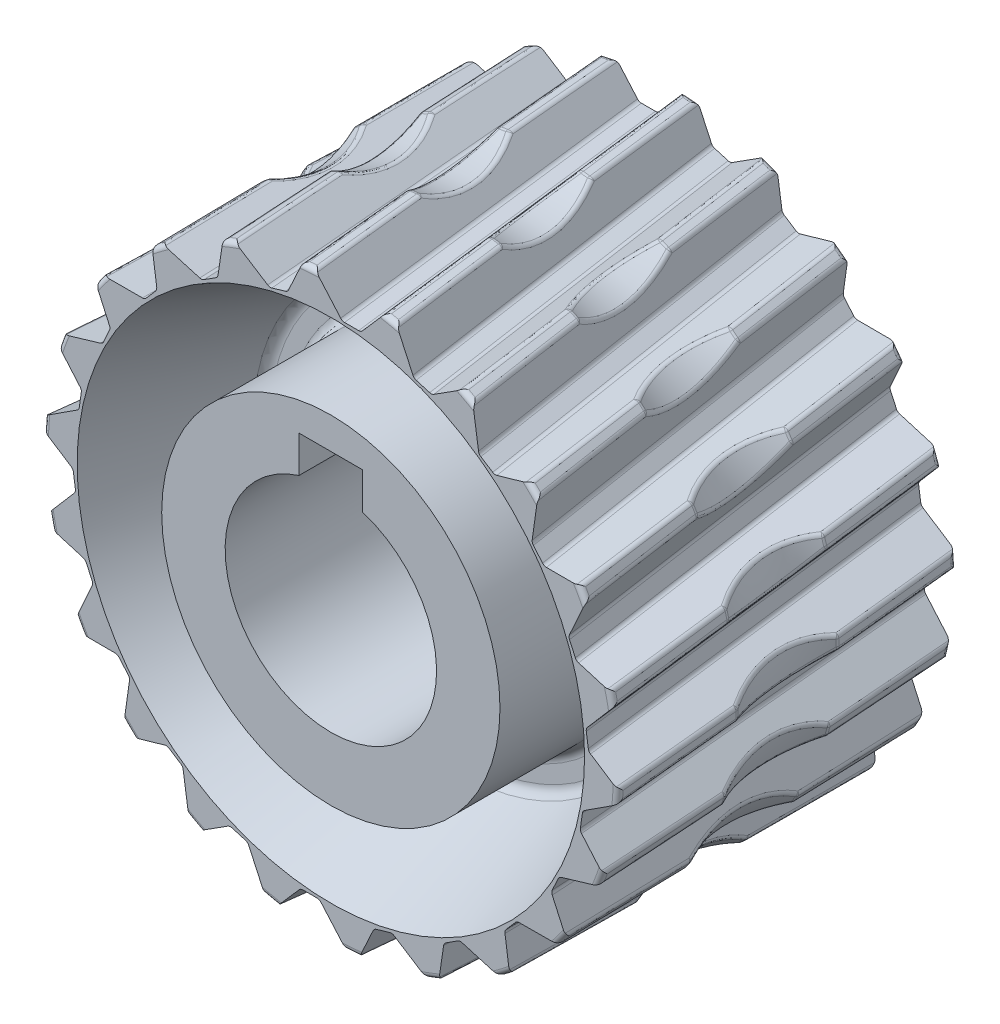
SolidWorks part; units mm, degrees
material "AISI 1020"
ref_plane "Front Plane" through (0, 0, 0) normal (0, 0, 1) x (1, 0, 0)
ref_plane "Top Plane" through (0, 0, 0) normal (0, 1, 0) x (1, 0, 0)
ref_plane "Right Plane" through (0, 0, 0) normal (1, 0, 0) x (0, 0, -1)
sketch "Base Sketch" plane through (0, 0, 0) normal (0, 0, 1) x (1, 0, 0)
  circle A0 centre (0, 0) radius 28.575
  circle A1 centre (0, 0) radius 7.9375
  dimension "D1" = 57.15
  dimension "D2" = 15.875
extrude "Base" add sketch "Base Sketch" along normal mid plane 25.4
sketch "Groove Sketch" plane through (0, 0, 0) normal (1, 0, 0) x (0, 0, -1)
  line L0 (12.7, 28.575) -> (-12.7, 28.575) construction
  line L1 (0, 0) -> (25.0554, 0) construction
  circle A0 centre (0, 28.575) radius 7.9375
  dimension "D1" = 15.875
revolve "Groove" cut sketch "Groove Sketch" angle 360 about L1
sketch "Revolved Sketch" plane through (0, 0, 0) normal (1, 0, 0) x (0, 0, -1)
  line L0 (12.7, 12.7) -> (2.54, 12.7)
  line L1 (12.7, -28.575) -> (12.7, 28.575) construction
  line L2 (2.54, 12.7) -> (2.54, 15.24)
  line L3 (2.54, 15.24) -> (12.7, 19.05)
  line L4 (12.7, 19.05) -> (12.7, 12.7)
  line L5 (0, 0) -> (27.599, 0) construction
  line L6 (0, 0) -> (0, 38.1046) construction
  line L7 (-12.7, 19.05) -> (-12.7, 12.7)
  line L8 (-12.7, 12.7) -> (-2.54, 12.7)
  line L9 (-2.54, 12.7) -> (-2.54, 15.24)
  line L10 (-2.54, 15.24) -> (-12.7, 19.05)
  dimension "D1" = 2.54
  dimension "D2" = 10.16
  dimension "D3" = 38.1
  dimension "D4" = 25.4
revolve "Inner Revolved Cut" cut sketch "Revolved Sketch" angle 360 about L5
chamfer "Outer Chamfer" distance 2.54 angle 45 2 edges at (28.575, 0, -12.7) (28.575, 0, 12.7)
fillet "Inner Fillet" radius 0.7874 4 edges at (15.24, 0, -2.54) (12.7, 0, -2.54) (12.7, 0, 2.54) (15.24, 0, 2.54)
sketch "Keyway Sketch" plane through (0, 0, 0) normal (0, 0, 1) x (1, 0, 0)
  line L1 (2.3876, 0) -> (-2.3876, 0)
  line L2 (2.3876, 0) -> (2.3876, 10.3251)
  line L3 (2.3876, 10.3251) -> (-2.3876, 10.3251)
  line L4 (-2.3876, 0) -> (-2.3876, 10.3251)
  line L5 (2.3876, 0) -> (-2.3876, 10.3251) construction
  line L6 (2.3876, 10.3251) -> (-2.3876, 0) construction
  circle A1 centre (0, 0) radius 7.9375 construction
  point P0 (0, 5.1626)
  dimension "D1" = 4.7752
  dimension "D2" = 2.3876
extrude "Keyway" cut sketch "Keyway Sketch" against normal through all and the other way through all
ref_plane "Hovering Plane" through (0, 24.13, 0) normal (0, 1, 0) x (1, 0, 0)
sketch "Path" plane through (0, 24.13, 0) normal (0, 1, 0) x (1, 0, 0)
  line L0 (0, 12.7) -> (0, -12.7) construction
  line L1 (26.035, 12.7) -> (-26.035, 12.7) construction
  line L2 (-26.035, -12.7) -> (26.035, -12.7) construction
  line L3 (1.9492, -15.875) -> (-1.9492, 15.875)
  point P10 (0, 0)
  dimension "D1" = 7
  dimension "D2" = 3.175
ref_plane "Profile Plane" through (1.9492, 24.13, 15.875) normal (-0.1219, 0, -0.9925) x (-0.9925, 0, 0.1219)
sketch "Revolve Sketch" plane through (0, 0, 0) normal (1, 0, 0) x (0, 0, -1)
  line L0 (0, 0) -> (-12.7, 0) construction
  line L1 (7.9375, 28.575) -> (12.7, 28.575)
  line L2 (12.7, 28.575) -> (12.7, 21.59)
  line L3 (12.7, -26.035) -> (12.7, 26.035) construction
  line L4 (12.7, 21.59) -> (-12.7, 21.59)
  line L5 (-12.7, 26.035) -> (-12.7, -26.035) construction
  line L6 (-12.7, 21.59) -> (-12.7, 28.575)
  line L7 (-12.7, 28.575) -> (7.9375, 28.575)
  line L8 (-12.7, 0) -> (12.7, 0) construction
  dimension "D1" = 43.18
  dimension "D2" = 6.985
  dimension "D3" = 6.985
sketch "Sketch3" plane through (1.9492, 24.13, 15.875) normal (-0.1219, 0, -0.9925) x (-0.9925, 0, 0.1219)
  line L0 (0.6985, -4.9022) -> (-0.6985, -4.9022)
  line L1 (-0.6985, -4.9022) -> (-4.9471, 0)
  line L2 (-4.9471, 0) -> (4.9471, 0)
  line L3 (4.9471, 0) -> (0.6985, -4.9022)
  point P2 (-2.3495, -2.9972)
  point P5 (2.3495, -2.9972)
  point P6 (0, 0)
  point P7 (0, 0)
  dimension "D1" = 2.9972
  dimension "D2" = 1.397
  dimension "D3" = 1.905
  dimension "D4" = 4.699
sweep "Triangle Cut" cut profiles "Sketch3" path "Path"
revolve "Revolve Cut" cut sketch "Revolve Sketch" angle 360 about L0
fillet "Revolved Fillet" radius 0.381 2 edges at (-0.7037, 19.2278, 0) (0.7037, 19.2278, 0)
pattern_circular "Gears" count 22 over 360 about axis through (0, 0, -12.7) along (0, 0, 1) of "Triangle Cut", "Revolved Fillet"
fillet "Groove Fillet" radius 0.381 220 edges at (3.5213, 21.3009, 8.204) (2.6225, 21.4301, -8.204) (4.4401, 21.1285, 8.2746) (4.472, 21.1218, 12.7) (1.6924, 21.5236, -8.2746) (1.6598, 21.5261, -12.7) (-3.5213, 21.3009, -8.204) (-2.6225, 21.4301, 8.204) (-4.4401, 21.1285, -8.2746) (-4.472, 21.1218, -12.7) (-1.6924, 21.5236, 8.2746) (-1.6598, 21.5261, 12.7) (-9.3798, 19.446, -8.204) (-7.6877, 20.1749, 8.2746) (-8.5539, 19.8232, 8.204) (-10.2128, 19.0217, -8.2746) (-10.2416, 19.0063, -12.7) (-7.6572, 20.1865, 12.7) (-14.4784, 16.0157, -8.204) (-13.0602, 17.1918, 8.2746) (-13.7922, 16.6103, 8.204) (-15.1582, 15.3739, -8.2746) (-15.1814, 15.351, -12.7) (-13.0342, 17.2116, 12.7) (-18.4041, 11.2879, -8.204) (-17.3747, 12.8159, 8.2746) (-17.9132, 12.0518, 8.204) (-18.8755, 10.4806, -8.2746) (-18.8913, 10.4521, -12.7) (-17.3553, 12.8422, 12.7) (-20.8388, 5.6457, -8.204) (-20.2816, 7.4018, 8.2746) (-20.583, 6.5169, 8.204) (-21.0636, 4.7383, -8.2746) (-21.0708, 4.7064, -12.7) (-20.2703, 7.4325, 12.7) (-21.5852, -0.454, -8.204) (-21.5453, 1.388, 8.2746) (-21.5852, 0.454, 8.204) (-21.5453, -1.388, -8.2746) (-21.5432, -1.4206, -12.7) (-21.5432, 1.4206, 12.7) (-20.583, -6.5169, -8.204) (-21.0636, -4.7383, 8.2746) (-20.8388, -5.6457, 8.204) (-20.2816, -7.4018, -8.2746) (-20.2703, -7.4325, -12.7) (-21.0708, -4.7064, 12.7) (-17.9132, -12.0518, -8.204) (-18.8755, -10.4806, 8.2746) (-18.4041, -11.2879, 8.204) (-17.3747, -12.8159, -8.2746) (-17.3553, -12.8422, -12.7) (-18.8913, -10.4521, 12.7) (-13.7922, -16.6103, -8.204) (-15.1582, -15.3739, 8.2746) (-14.4784, -16.0157, 8.204) (-13.0602, -17.1918, -8.2746) (-13.0342, -17.2116, -12.7) (-15.1814, -15.351, 12.7) (-8.5539, -19.8232, -8.204) (-10.2128, -19.0217, 8.2746) (-9.3798, -19.446, 8.204) (-7.6877, -20.1749, -8.2746) (-7.6572, -20.1865, -12.7) (-10.2416, -19.0063, 12.7) (-2.6225, -21.4301, -8.204) (-4.4401, -21.1285, 8.2746) (-3.5213, -21.3009, 8.204) (-1.6924, -21.5236, -8.2746) (-1.6598, -21.5261, -12.7) (-4.472, -21.1218, 12.7) (3.5213, -21.3009, -8.204) (1.6924, -21.5236, 8.2746) (2.6225, -21.4301, 8.204) (4.4401, -21.1285, -8.2746) (4.472, -21.1218, -12.7) (1.6598, -21.5261, 12.7) (9.3798, -19.446, -8.204) (7.6877, -20.1749, 8.2746) (8.5539, -19.8232, 8.204) (10.2128, -19.0217, -8.2746) (10.2416, -19.0063, -12.7) (7.6572, -20.1865, 12.7) (14.4784, -16.0157, -8.204) (13.0602, -17.1918, 8.2746) (13.7922, -16.6103, 8.204) (15.1582, -15.3739, -8.2746) (15.1814, -15.351, -12.7) (13.0342, -17.2116, 12.7) (18.4041, -11.2879, -8.204) (17.3747, -12.8159, 8.2746) (17.9132, -12.0518, 8.204) (18.8755, -10.4806, -8.2746) (18.8913, -10.4521, -12.7) (17.3553, -12.8422, 12.7) (20.8388, -5.6457, -8.204) (20.2816, -7.4018, 8.2746) (20.583, -6.5169, 8.204) (21.0636, -4.7383, -8.2746) (21.0708, -4.7064, -12.7) (20.2703, -7.4325, 12.7) (21.5852, 0.454, -8.204) (21.5453, -1.388, 8.2746) (21.5852, -0.454, 8.204) (21.5453, 1.388, -8.2746) (21.5432, 1.4206, -12.7) (21.5432, -1.4206, 12.7) (20.583, 6.5169, -8.204) (21.0636, 4.7383, 8.2746) (20.8388, 5.6457, 8.204) (20.2816, 7.4018, -8.2746) (20.2703, 7.4325, -12.7) (21.0708, 4.7064, 12.7) (17.9132, 12.0518, -8.204) (18.8755, 10.4806, 8.2746) (18.4041, 11.2879, 8.204) (17.3747, 12.8159, -8.2746) (17.3553, 12.8422, -12.7) (18.8913, 10.4521, 12.7) (13.7922, 16.6103, -8.204) (15.1582, 15.3739, 8.2746) (14.4784, 16.0157, 8.204) (13.0602, 17.1918, -8.2746) (13.0342, 17.2116, -12.7) (15.1814, 15.351, 12.7) (8.5539, 19.8232, -8.204) (10.2128, 19.0217, 8.2746) (9.3798, 19.446, 8.204) (7.6877, 20.1749, -8.2746) (7.6572, 20.1865, -12.7) (10.2416, 19.0063, 12.7) (3.489, 21.3062, 3.7701) (1.872, 20.5529, 0.0907) (2.655, 21.4261, -3.7701) (4.0832, 20.2915, 0.9802) (-3.489, 21.3062, -3.7701) (-1.872, 20.5529, -0.0907) (-2.655, 21.4261, 3.7701) (-4.0832, 20.2915, -0.9802) (-9.3504, 19.4602, -3.7701) (-7.5354, 19.2778, 0.9802) (-8.5838, 19.8102, 3.7701) (-9.6346, 18.3192, -0.9802) (-14.4542, 16.0376, -3.7701) (-12.6614, 16.374, 0.9802) (-13.8173, 16.5894, 3.7701) (-14.4054, 14.8627, -0.9802) (-18.387, 11.3158, -3.7701) (-16.7616, 12.1436, 0.9802) (-17.9314, 12.0247, 3.7701) (-18.0092, 10.2022, -0.9802) (-20.8302, 5.6772, -3.7701) (-19.5039, 6.9294, 0.9802) (-20.5928, 6.4857, 3.7701) (-20.154, 4.7152, -0.9802) (-21.5859, -0.4213, -3.7701) (-20.6661, 1.1539, 0.9802) (-21.5859, 0.4213, 3.7701) (-20.6661, -1.1539, -0.9802) (-20.5928, -6.4857, -3.7701) (-20.154, -4.7152, 0.9802) (-20.8302, -5.6772, 3.7701) (-19.5039, -6.9294, -0.9802) (-17.9314, -12.0247, -3.7701) (-18.0092, -10.2022, 0.9802) (-18.387, -11.3158, 3.7701) (-16.7616, -12.1436, -0.9802) (-13.8173, -16.5894, -3.7701) (-14.4054, -14.8627, 0.9802) (-14.4542, -16.0376, 3.7701) (-12.6614, -16.374, -0.9802) (-8.5838, -19.8102, -3.7701) (-9.6346, -18.3192, 0.9802) (-9.3504, -19.4602, 3.7701) (-7.5354, -19.2778, -0.9802) (-2.655, -21.4261, -3.7701) (-4.0832, -20.2915, 0.9802) (-3.489, -21.3062, 3.7701) (-1.799, -20.6199, -0.9802) (3.489, -21.3062, -3.7701) (1.799, -20.6199, 0.9802) (2.655, -21.4261, 3.7701) (4.0832, -20.2915, -0.9802) (9.3504, -19.4602, -3.7701) (7.5354, -19.2778, 0.9802) (8.5838, -19.8102, 3.7701) (9.6346, -18.3192, -0.9802) (14.4542, -16.0376, -3.7701) (12.6614, -16.374, 0.9802) (13.8173, -16.5894, 3.7701) (14.4054, -14.8627, -0.9802) (18.387, -11.3158, -3.7701) (16.7616, -12.1436, 0.9802) (17.9314, -12.0247, 3.7701) (18.0092, -10.2022, -0.9802) (20.8302, -5.6772, -3.7701) (19.5039, -6.9294, 0.9802) (20.5928, -6.4857, 3.7701) (20.154, -4.7152, -0.9802) (21.5859, 0.4213, -3.7701) (20.6661, -1.1539, 0.9802) (21.5859, -0.4213, 3.7701) (20.6661, 1.1539, -0.9802) (20.5928, 6.4857, -3.7701) (20.154, 4.7152, 0.9802) (20.8302, 5.6772, 3.7701) (19.5039, 6.9294, -0.9802) (17.9314, 12.0247, -3.7701) (18.0092, 10.2022, 0.9802) (18.387, 11.3158, 3.7701) (16.7616, 12.1436, -0.9802) (13.8173, 16.5894, -3.7701) (14.4054, 14.8627, 0.9802) (14.4542, 16.0376, 3.7701) (12.6614, 16.374, -0.9802) (8.5838, 19.8102, -3.7701) (9.6346, 18.3192, 0.9802) (9.3504, 19.4602, 3.7701) (7.5354, 19.2778, -0.9802)
